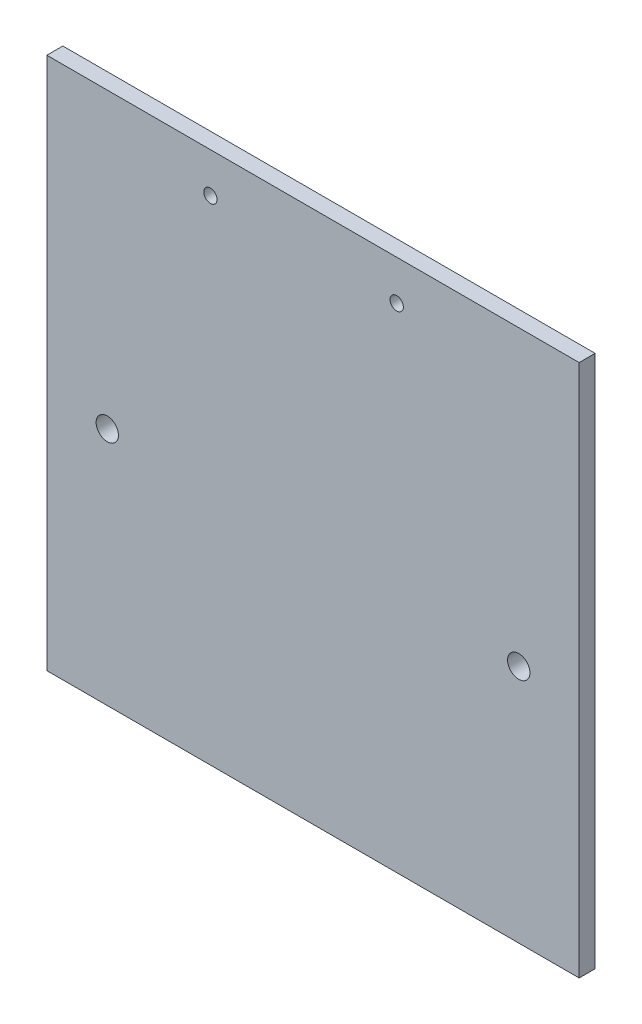
SolidWorks part; units mm, degrees
ref_plane "前视基准面" through (0, 0, 0) normal (0, 0, 1) x (1, 0, 0)
ref_plane "上视基准面" through (0, 0, 0) normal (0, 1, 0) x (1, 0, 0)
ref_plane "右视基准面" through (0, 0, 0) normal (1, 0, 0) x (0, 0, -1)
other "Configuration Table"
sketch "草图1" plane through (0, 0, 0) normal (0, 0, 1) x (1, 0, 0)
  line L1 (50, -93.5) -> (-50, -93.5)
  line L2 (50, -93.5) -> (50, 93.5)
  line L3 (50, 93.5) -> (-50, 93.5)
  line L4 (-50, -93.5) -> (-50, 93.5)
  line L5 (50, -93.5) -> (-50, 93.5) construction
  line L6 (50, 93.5) -> (-50, -93.5) construction
  point P0 (0, 0)
  dimension "D1" = 100
extrude "凸台-拉伸1" add sketch "草图1" along normal blind 3
sketch "草图2" plane through (0, 0, 3) normal (0, 0, 1) x (1, 0, 0)
  circle A0 centre (-38.6496, 13.6991) radius 2.1
  circle A1 centre (38.6496, 13.6991) radius 2.1
extrude "切除-拉伸1" cut sketch "草图2" against normal blind 10
sketch "草图3" plane through (0, 0, 3) normal (0, 0, 1) x (1, 0, 0)
  circle A0 centre (-19.2783, 61.3121) radius 1.25
  circle A1 centre (15.7217, 61.3121) radius 1.25
extrude "切除-拉伸2" cut sketch "草图3" against normal blind 10
sketch "草图4" plane through (0, 0, 3) normal (0, 0, 1) x (1, 0, 0)
  line L0 (-20.8063, 68.8121) -> (7.6796, 68.8121)
sketch "草图5" plane through (0, 0, 3) normal (0, 0, 1) x (1, 0, 0)
  line L0 (-50, 68.8121) -> (50, 68.8121)
  line L1 (-50, 93.5) -> (-50, -93.5) construction
  line L2 (50, -93.5) -> (50, 93.5) construction
  line L3 (50, 68.8121) -> (50, 93.5)
  line L4 (50, 93.5) -> (-50, 93.5)
  line L5 (-50, 93.5) -> (-50, 68.8121)
extrude "切除-拉伸3" cut sketch "草图5" against normal blind 10
sketch "草图6" plane through (0, 0, 3) normal (0, 0, 1) x (1, 0, 0)
  line L0 (-50, -31.3209) -> (50, -31.3209)
  line L1 (-50, 68.8121) -> (-50, -93.5) construction
  line L2 (50, -93.5) -> (50, 68.8121) construction
  line L3 (-50, -31.3209) -> (-50, -93.5)
  line L4 (-50, -93.5) -> (50, -93.5)
  line L5 (50, -93.5) -> (50, -31.3209)
extrude "切除-拉伸4" cut sketch "草图6" against normal blind 10
